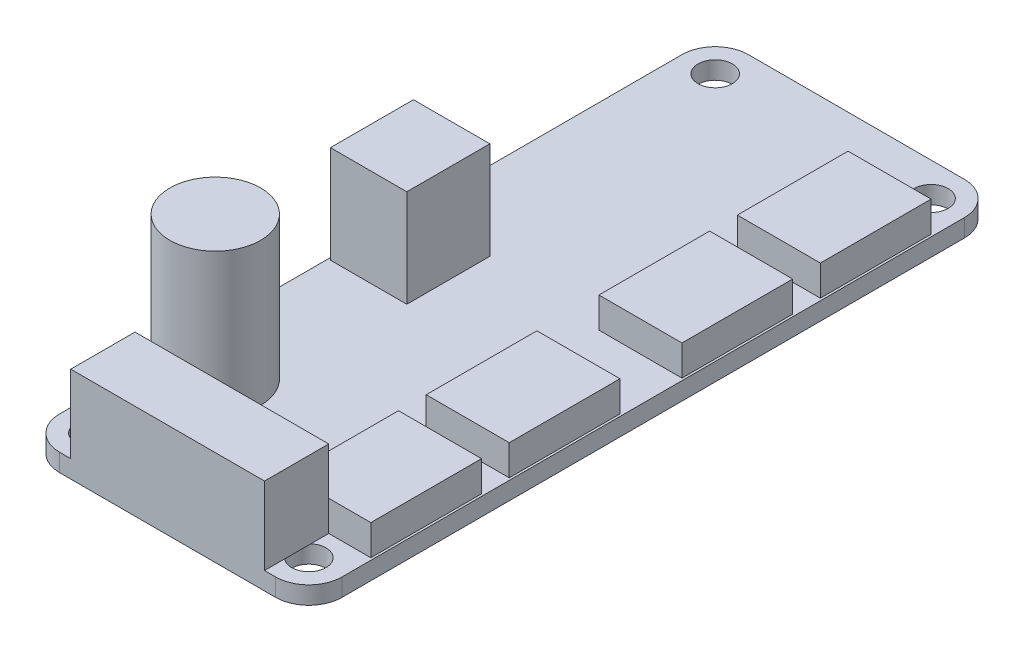
SolidWorks part; units mm, degrees
ref_plane "Front plane" through (0, 0, 0) normal (0, 0, 1) x (1, 0, 0)
ref_plane "Top plane" through (0, 0, 0) normal (0, 1, 0) x (1, 0, 0)
ref_plane "Right Plane" through (0, 0, 0) normal (1, 0, 0) x (0, 0, -1)
sketch "Sketch1" plane through (0, 0, 0) normal (0, 1, 0) x (1, 0, 0)
  line L1 (3, 0) -> (22.5, 0)
  line L2 (0, 3) -> (0, 59.2)
  line L3 (3, 62.2) -> (22.5, 62.2)
  line L4 (25.5, 3) -> (25.5, 59.2)
  arc A0 (0, 59.2) -> (3, 62.2) centre (3, 59.2) cw
  arc A1 (22.5, 62.2) -> (25.5, 59.2) centre (22.5, 59.2) cw
  arc A2 (22.5, 0) -> (25.5, 3) centre (22.5, 3) ccw
  arc A3 (3, 0) -> (0, 3) centre (3, 3) cw
  circle A4 centre (3, 59.2) radius 1.55
  circle A5 centre (22.5, 59.2) radius 1.55
  circle A6 centre (22.5, 3) radius 1.55
  circle A7 centre (3, 3) radius 1.55
  point P13 (0, 0)
  dimension "D3" = 3
  dimension "D4" = 3.1
  dimension "D1" = 62.2
  dimension "D2" = 25.5
extrude "Boss-Extrude1" add sketch "Sketch1" along normal blind 1.6
sketch "Sketch2" plane through (0, 1.6, 0) normal (0, 1, 0) x (1, 0, 0)
  line L0 (0, 59.2) -> (0, 3) construction
  line L1 (0.2, 34.75) -> (7.1, 34.75)
  line L2 (0.2, 34.75) -> (0.2, 27.25)
  line L3 (0.2, 27.25) -> (7.1, 27.25)
  line L4 (7.1, 34.75) -> (7.1, 27.25)
  line L5 (22.5, 62.2) -> (3, 62.2) construction
  point P8 (7.1, 31)
  dimension "D1" = 7.5
  dimension "D2" = 6.9
  dimension "D3" = 0.2
  dimension "D4" = 31.2
extrude "Boss-Extrude2" add sketch "Sketch2" along normal blind 8.8
sketch "Sketch3" plane through (0, 1.6, 0) normal (0, 1, 0) x (1, 0, 0)
  line L0 (3, 0) -> (22.5, 0) construction
  line L3 (0.2, 34.75) -> (0.2, 27.25) construction
  circle A0 centre (4.3, 12.75) radius 4.1
  dimension "D1" = 8.2
  dimension "D2" = 12.75
extrude "Boss-Extrude3" add sketch "Sketch3" along normal blind 12.9
sketch "Sketch4" plane through (0, 1.6, 0) normal (0, 1, 0) x (1, 0, 0)
  line L0 (3, 0) -> (22.5, 0) construction
  line L1 (25.3, 5.8) -> (17.8, 5.8)
  line L2 (25.3, 5.8) -> (25.3, 15.8)
  line L3 (25.3, 15.8) -> (17.8, 15.8)
  line L4 (17.8, 5.8) -> (17.8, 15.8)
  line L5 (25.3, 18.3) -> (17.8, 18.3)
  line L6 (25.3, 18.3) -> (25.3, 28.3)
  line L7 (25.3, 28.3) -> (17.8, 28.3)
  line L8 (17.8, 18.3) -> (17.8, 28.3)
  line L9 (25.3, 33.9) -> (17.8, 33.9)
  line L10 (25.3, 33.9) -> (25.3, 43.9)
  line L11 (25.3, 43.9) -> (17.8, 43.9)
  line L12 (17.8, 33.9) -> (17.8, 43.9)
  line L13 (25.3, 46.4) -> (17.8, 46.4)
  line L14 (25.3, 46.4) -> (25.3, 56.4)
  line L15 (25.3, 56.4) -> (17.8, 56.4)
  line L16 (17.8, 46.4) -> (17.8, 56.4)
  line L17 (22.5, 62.2) -> (3, 62.2) construction
  line L18 (25.5, 3) -> (25.5, 59.2) construction
  dimension "D1" = 10
  dimension "D2" = 7.5
  dimension "D3" = 5.8
  dimension "D4" = 5.8
  dimension "D5" = 2.5
  dimension "D6" = 2.5
  dimension "D7" = 0.2
extrude "Boss-Extrude4" add sketch "Sketch4" along normal blind 2.75
sketch "Sketch6" plane through (0, 1.6, 0) normal (0, 1, 0) x (1, 0, 0)
  line L0 (3, 0) -> (22.5, 0) construction
  line L1 (21.5, 0) -> (4, 0)
  line L2 (21.5, 0) -> (21.5, 5.8)
  line L3 (21.5, 5.8) -> (4, 5.8)
  line L4 (4, 0) -> (4, 5.8)
  point P6 (12.75, 0)
  dimension "D1" = 17.5
  dimension "D2" = 5.8
extrude "Boss-Extrude5" add sketch "Sketch6" along normal blind 7
